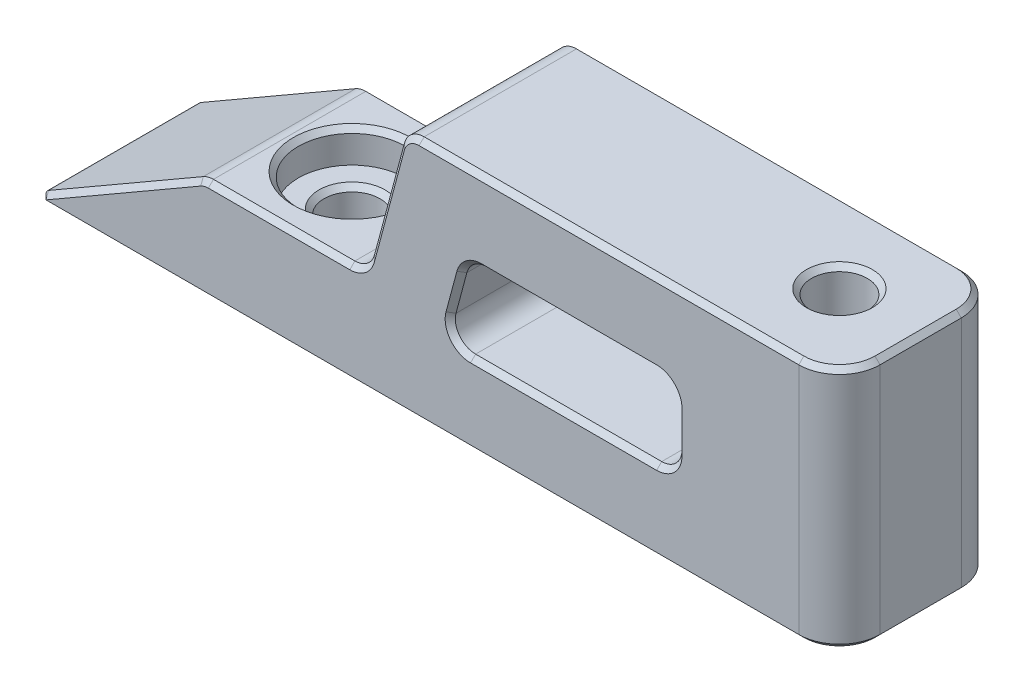
SolidWorks part; units mm, degrees
ref_plane "Front Plane" through (0, 0, 0) normal (0, 0, 1) x (1, 0, 0)
ref_plane "Top Plane" through (0, 0, 0) normal (0, 1, 0) x (1, 0, 0)
ref_plane "Right Plane" through (0, 0, 0) normal (1, 0, 0) x (0, 0, -1)
sketch "Sketch1" plane through (0, 0, 0) normal (0, 0, 1) x (1, 0, 0)
  line L0 (-31.75, 0) -> (31.75, 0)
  line L1 (31.75, 0) -> (31.75, 19.05)
  line L3 (-5.3018, 7.9375) -> (-18.0018, 7.9375)
  line L4 (-18.0018, 7.9375) -> (-31.75, 0)
  line L5 (-5.3018, 7.9375) -> (-2.3243, 19.05)
  line L6 (-2.3243, 19.05) -> (31.75, 19.05)
  line L7 (19.05, 12.7) -> (19.05, 6.35)
  line L8 (19.05, 6.35) -> (0.8468, 6.35)
  line L9 (0.8468, 6.35) -> (2.5483, 12.7)
  line L10 (2.5483, 12.7) -> (19.05, 12.7)
  dimension "D1" = 31.75
  dimension "D2" = 7.9375
  dimension "D3" = 30
  dimension "D4" = 12.7
  dimension "D5" = 75
  dimension "D6" = 31.75
  dimension "D7" = 19.05
  dimension "D8" = 6.35
  dimension "D9" = 6.35
  dimension "D10" = 6.35
  dimension "D11" = 12.7
extrude "Boss-Extrude1" add sketch "Sketch1" along normal mid plane 12.7
sketch "Sketch2" plane through (0, 0, 0) normal (0, -1, 0) x (1, 0, 0)
  circle A0 centre (-12.7, 0) radius 2.1828
  circle A1 centre (25.4, 0) radius 2.1828
  dimension "D3" = 4.3656
  dimension "D4" = 4.3656
  dimension "D1" = 12.7
  dimension "D2" = 25.4
extrude "Cut-Extrude1" cut sketch "Sketch2" against normal through all both and the other way through all
sketch "Sketch3" plane through (0, 7.9375, 0) normal (0, 1, 0) x (1, 0, 0)
  circle A0 centre (-12.7, 0) radius 4.191
  dimension "D1" = 8.382
extrude "Cut-Extrude2" cut sketch "Sketch3" against normal blind 2.54
fillet "Fillet1" radius 0.3969 1 edges at (-31.75, 0, 0)
fillet "Fillet2" radius 1.5875 7 edges at (-5.3018, 7.9375, 0) (-18.0018, 7.9375, 0) (-2.3243, 19.05, 0) (0.8468, 6.35, 0) (2.5483, 12.7, 0) (19.05, 12.7, 0) (19.05, 6.35, 0)
fillet "Fillet3" radius 3.175 2 edges at (31.75, 9.525, -6.35) (31.75, 9.525, 6.35)
chamfer "Chamfer1" distance 0.3969 angle 45 45 edges at (-14.8828, 5.3975, 0) (-12.7, 0, 2.1828) (25.4, 0, 2.1828) (25.4, 19.05, -2.1828) (2.8, 12.3719, 6.35) (1.8076, 9.9359, 6.35) (1.6562, 6.9711, 6.35) (10.1891, 6.35, 6.35) (18.585, 6.815, 6.35) (19.05, 9.525, 6.35) (18.585, 12.235, 6.35) (10.6144, 12.7, 6.35) (-12.0482, 7.9375, -6.35) (-5.5536, 8.2656, -6.35) (-17.9874, 7.8834, -6.35) (-3.8131, 13.4938, -6.35) (-24.4188, 4.2327, -6.35) (-2.0725, 18.7219, -6.35) (-30.6522, 0.2942, -6.35) (13.7344, 19.05, -6.35) (-0.8469, 0, -6.35) (30.8201, 19.05, -5.4201) (30.8201, 0, -5.4201) (31.75, 19.05, 0) (31.75, 0, 0) (30.8201, 19.05, 5.4201) (30.8201, 0, 5.4201) (13.7344, 19.05, 6.35) (-2.0725, 18.7219, 6.35) (-3.8131, 13.4938, 6.35) (-5.5536, 8.2656, 6.35) (-12.0482, 7.9375, 6.35) (-17.9874, 7.8834, 6.35) (-24.4188, 4.2327, 6.35) (-30.6522, 0.2942, 6.35) (-0.8469, 0, 6.35) (-16.891, 7.9375, 0) (10.6144, 12.7, -6.35) (2.8, 12.3719, -6.35) (18.585, 12.235, -6.35) (1.8076, 9.9359, -6.35) (19.05, 9.525, -6.35) (1.6562, 6.9711, -6.35) (18.585, 6.815, -6.35) (10.1891, 6.35, -6.35)
